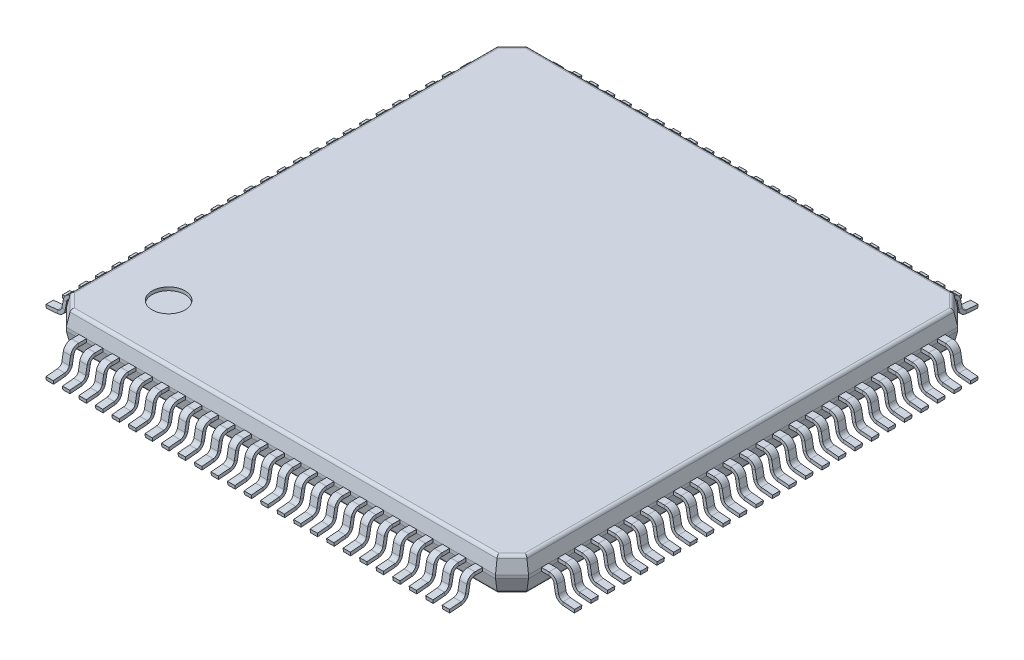
SolidWorks part; units mm, degrees
ref_plane "Front" through (0, 0, 0) normal (0, 0, 1) x (1, 0, 0)
ref_plane "Top" through (0, 0, 0) normal (0, 1, 0) x (1, 0, 0)
ref_plane "Right" through (0, 0, 0) normal (1, 0, 0) x (0, 0, -1)
sketch "Эскиз1" plane through (0, 0, 0) normal (0, 1, 0) x (1, 0, 0)
  line L0 (0, 13.5) -> (0.5, 14)
  line L1 (0.5, 0) -> (13.5, 0)
  line L2 (0, 0.5) -> (0, 13.5)
  line L3 (0.5, 14) -> (13.5, 14)
  line L4 (14, 0.5) -> (14, 13.5)
  line L5 (13.5, 14) -> (14, 13.5)
  line L6 (0, 0.5) -> (0.5, 0)
  line L7 (13.5, 0) -> (14, 0.5)
  point P0 (0, 0)
  point P1 (14, 14)
  point P2 (0, 14)
  point P3 (14, 0)
  dimension "D1" = 14
  dimension "D2" = 14
extrude "Бобышка-Вытянуть1" add sketch "Эскиз1" along normal blind 1
chamfer "Фаска1" distance 0.45 angle 12 8 edges at (0.25, 1, -13.75) (7, 1, -14) (13.75, 1, -13.75) (14, 1, -7) (13.75, 1, -0.25) (7, 1, 0) (0.25, 1, -0.25) (0, 1, -7) first distance on face at (0.25, 0.5, -13.75) first distance on face at (7, 0.5, -14) first distance on face at (13.75, 0.5, -13.75) first distance on face at (14, 0.5, -7) first distance on face at (13.75, 0.5, -0.25) first distance on face at (7, 0.5, 0) first distance on face at (0.25, 0.5, -0.25) first distance on face at (0, 0.5, -7)
chamfer "Фаска2" distance 0.45 angle 12 8 edges at (0.25, 0, -0.25) (7, 0, 0) (13.75, 0, -0.25) (14, 0, -7) (13.75, 0, -13.75) (7, 0, -14) (0.25, 0, -13.75) (0, 0, -7) first distance on face at (0.25, 0.275, -0.25) first distance on face at (7, 0.275, 0) first distance on face at (13.75, 0.275, -0.25) first distance on face at (14, 0.275, -7) first distance on face at (13.75, 0.275, -13.75) first distance on face at (7, 0.275, -14) first distance on face at (0.25, 0.275, -13.75) first distance on face at (0, 0.275, -7)
fillet "Скругление1" radius 0.1 16 edges at (13.6824, 1, -13.6824) (13.9043, 1, -7) (13.6824, 1, -0.3176) (7, 1, -0.0957) (0.3176, 1, -0.3176) (0.0957, 1, -7) (0.3176, 1, -13.6824) (7, 1, -13.9043) (13.6824, 0, -0.3176) (13.9043, 0, -7) (13.6824, 0, -13.6824) (7, 0, -13.9043) (0.3176, 0, -13.6824) (0.0957, 0, -7) (0.3176, 0, -0.3176) (7, 0, -0.0957)
sketch "Эскиз2" plane through (0, 1, 0) normal (0, 1, 0) x (1, 0, 0)
  line L0 (0, 0.5) -> (0, 13.5) construction
  line L1 (13.5, 0) -> (0.5, 0) construction
  circle A0 centre (1.8, 1.8) radius 0.5
  dimension "D2" = 1.8
  dimension "D3" = 1
  dimension "D1" = 1.8
extrude "Вырез-Вытянуть1" cut sketch "Эскиз2" against normal blind 0.1
ref_plane "Плоскость1" through (1, 0, 0) normal (-1, 0, 0) x (0, 0, 1)
sketch "Эскиз3" plane through (1, 0, 0) normal (-1, 0, 0) x (0, 0, 1)
  line L0 (0, 0.5) -> (0.2327, 0.5)
  line L1 (0.4296, 0.3354) -> (0.4729, 0.0943)
  line L2 (0.6524, -0.0696) -> (1, -0.1)
  line L3 (-0.5732, 0) -> (-13.4268, 0) construction
  arc A0 (0.2327, 0.5) -> (0.4296, 0.3354) centre (0.2327, 0.3) cw
  arc A1 (0.4729, 0.0943) -> (0.6524, -0.0696) centre (0.6698, 0.1297) ccw
  point P9 (0.4, 0.5)
  point P12 (0.5, -0.0563)
  dimension "D7" = 0.2
  dimension "D1" = 5
  dimension "D2" = 0.05
  dimension "D3" = 1
  dimension "D4" = 0.1
  dimension "D5" = 0.5
  dimension "D6" = 0.6
sketch "Эскиз4" plane through (0, 0, 0) normal (0, 0, 1) x (1, 0, 0)
  line L0 (13.5, 0.55) -> (0.5, 0.55) construction
  line L1 (0.89, 0.45) -> (1.11, 0.45)
  line L2 (0.89, 0.45) -> (0.89, 0.55)
  line L3 (0.89, 0.55) -> (1.11, 0.55)
  line L4 (1.11, 0.45) -> (1.11, 0.55)
  line L5 (0.89, 0.45) -> (1.11, 0.55) construction
  line L6 (0.89, 0.55) -> (1.11, 0.45) construction
  point P0 (1, 0.5)
  dimension "D1" = 0.22
sweep "По траектории1" add profiles "Эскиз4" path "Эскиз3"
pattern_linear "Линейный массив1" count 25 spacing 0.5 along (1, 0, 0) of "По траектории1"
ref_plane "Плоскость2" through (0, 0, -7) normal (0, 0, -1) x (-1, 0, 0)
mirror "Зеркальное отражение1" about plane through (0, 0, -7) normal (0, 0, -1) of "По траектории1", "Линейный массив1"
ref_plane "Плоскость4" through (0, 0, -1) normal (0, 0, 1) x (1, 0, 0)
sketch "Эскиз6" plane through (0, 0, -1) normal (0, 0, 1) x (1, 0, 0)
  line L0 (14, 0.5) -> (14.2327, 0.5)
  line L1 (14.4296, 0.3354) -> (14.4729, 0.0943)
  line L2 (14.6524, -0.0696) -> (15, -0.1)
  arc A0 (14.2327, 0.5) -> (14.4296, 0.3354) centre (14.2327, 0.3) cw
  arc A1 (14.4729, 0.0943) -> (14.6524, -0.0696) centre (14.6698, 0.1297) ccw
  point P9 (14.4, 0.5)
  point P12 (14.5, -0.0563)
  dimension "D7" = 0.2
  dimension "D1" = 0
  dimension "D2" = 0.05
  dimension "D3" = 1
  dimension "D5" = 0.5
  dimension "D6" = 0.6
sketch "Эскиз5" plane through (14, -0.1278, 1.891) normal (1, 0, 0) x (0, 0.0872, -0.9962)
  line L0 (15.3915, -0.6662) -> (2.4409, 0.4668) construction
  line L1 (2.8207, 0.3332) -> (3.0399, 0.314)
  line L2 (2.8207, 0.3332) -> (2.8295, 0.4328)
  line L3 (2.8295, 0.4328) -> (3.0486, 0.4136)
  line L4 (3.0399, 0.314) -> (3.0486, 0.4136)
  line L5 (2.8207, 0.3332) -> (3.0486, 0.4136) construction
  line L6 (2.8295, 0.4328) -> (3.0399, 0.314) construction
  line L7 (2.4322, 0.3672) -> (15.3828, -0.7659) construction
  line L8 (2.4409, 0.4668) -> (2.4322, 0.3672) construction
  point P0 (2.9347, 0.3734)
  dimension "D1" = 0.22
sweep "По траектории2" add profiles "Эскиз5" path "Эскиз6"
pattern_linear "Линейный массив2" count 25 spacing 0.5 along (0, 0, -1) of "По траектории2"
ref_plane "Плоскость5" through (7, 0, 0) normal (1, 0, 0) x (0, 0, -1)
mirror "Зеркальное отражение2" about plane through (7, 0, 0) normal (1, 0, 0) of "По траектории2", "Линейный массив2"
